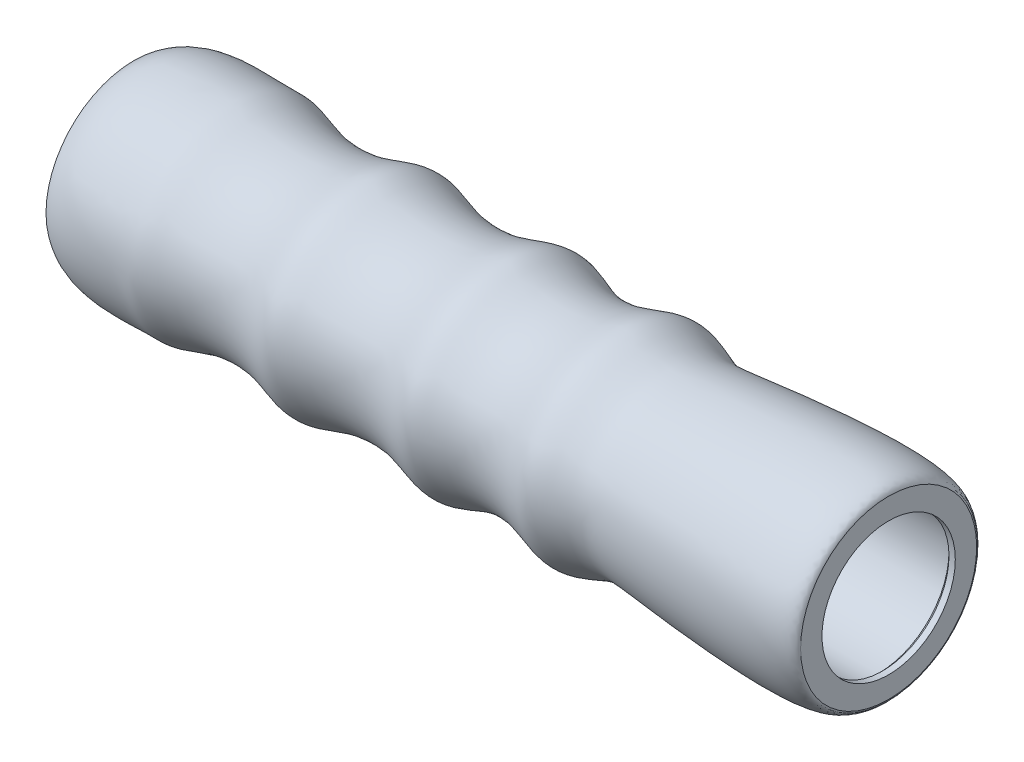
SolidWorks part; units mm, degrees
ref_plane "Front Plane" through (0, 0, 0) normal (0, 0, 1) x (1, 0, 0)
ref_plane "Top Plane" through (0, 0, 0) normal (0, 1, 0) x (1, 0, 0)
ref_plane "Right Plane" through (0, 0, 0) normal (1, 0, 0) x (0, 0, -1)
sketch "Sketch1" plane through (0, 0, 0) normal (1, 0, 0) x (0, 0, -1)
  circle A0 centre (0, 0) radius 11.2
  circle A1 centre (0, 0) radius 13.5
  dimension "D1" = 22.4
  dimension "D2" = 27
extrude "Boss-Extrude1" add sketch "Sketch1" along normal blind 60
sketch "Sketch2" plane through (0, 0, 0) normal (0, 0, 1) x (1, 0, 0)
  line L0 (8, 12.6) -> (8, 9.6)
  line L1 (8, 9.6) -> (11, 9.6)
  line L2 (0, 13.5) -> (0, -13.5) construction
  arc A0 (8, 12.6) -> (11, 9.6) centre (8, 9.6) cw
  dimension "D1" = 3
  dimension "D2" = 12.6
  dimension "D3" = 8
revolve "Cut-Revolve1" cut sketch "Sketch2" angle 360 about L0
pattern_circular "CirPattern1" count 8 over 360 about axis through (60, 0, 0) along (-1, 0, 0) of "Cut-Revolve1" reverse direction yes
pattern_linear "LPattern1" count 3 spacing 20 along (1, 0, 0) of "CirPattern1"
fillet "Fillet1" radius 3 1 edges at (0, 0, -11.2)
sketch "Sketch3" plane through (0, 0, 0) normal (0, 0, 1) x (1, 0, 0)
  line L1 (60, 11.2) -> (120, 11.2)
  line L3 (0, 14) -> (120, 14) construction
  line L4 (0, 0) -> (120, 0) construction
  line L5 (15, 16) -> (120, 16) construction
  line L6 (0, 14) -> (0, 13.5)
  line L8 (120, 11.2) -> (120, 14)
  line L9 (0, 13.5) -> (60, 13.5)
  line L10 (60, 13.5) -> (60, 11.2)
  line L11 (70.4326, 69.028) -> (-70.4326, -41.028) construction
  line L12 (16.7427, 16) -> (12.1026, 16) construction
  line L13 (31.0911, 14) -> (20.9785, 14) construction
  line L14 (38.2956, 16) -> (35.3687, 16) construction
  line L15 (51.885, 14) -> (43.5222, 14) construction
  line L16 (60.2588, 16) -> (56.7229, 16) construction
  line L17 (71.3792, 14) -> (64.9063, 14) construction
  line L18 (79.584, 16) -> (76.296, 16) construction
  line L19 (89.3552, 14) -> (82.2834, 14) construction
  line L20 (131.7118, -52.421) -> (107.7046, 83.7304) construction
  spline S0 degree 3 poles (0, 14) (3.546, 16.7705) (11.4825, 15.7663) (17.1109, 16.1703) (20.8304, 13.9736) (31.2475, 13.9921) (34.5996, 15.9651) (39.0064, 16.0624) (42.5633, 14.0034) (52.981, 13.9646) (56.3857, 15.8899) (60.7751, 16.1131) (64.1715, 13.9525) (72.258, 14.0158) (75.9733, 16.0157) (80.0369, 16.0183) (83.8613, 13.7538) (92.0811, 14.4865) (119.4009, 17.3976) (120, 14) knots 0 0 0 0 0.149508 0.178018 0.273199 0.29714 0.393483 0.415958 0.499414 0.519547 0.597158 0.613972 0.670877 0.68576 0.74792 0.763484 0.825842 0.850273 1 1 1 1
  point P9 (48, 14)
  point P10 (26, 14)
  point P12 (68, 14)
  dimension "D11" = 38
  dimension "D14" = 15
  dimension "D15" = 18.5
  dimension "D16" = 33
  dimension "D17" = 15
  dimension "D18" = 15
  dimension "D19" = 14
  dimension "D20" = 33
  dimension "D21" = 26
  dimension "D22" = 27
  dimension "D23" = 11.5
  dimension "D1" = 22
  dimension "D2" = 14
  dimension "D3" = 26
  dimension "D4" = 22
  dimension "D5" = 20
  dimension "D6" = 18
  dimension "D7" = 22
  dimension "D8" = 16
  dimension "D9" = 15
  dimension "D10" = 19
  dimension "D12" = 11.2
  dimension "D13" = 120
  dimension "D24" = 80
revolve "Revolve1" add sketch "Sketch3" angle 360 about L4
sketch "Sketch4" plane through (120, 0, 0) normal (1, 0, 0) x (0, 0, -1)
  circle A0 centre (0, 0) radius 11.2 construction
  circle A1 centre (0, 0) radius 11.2
  circle A2 centre (0, 0) radius 10.6
  dimension "D1" = 0.6
extrude "Boss-Extrude2" add sketch "Sketch4" against normal blind 1
chamfer "Chamfer1" distance 0.6 angle 45 1 edges at (119, 0, -11.2)
